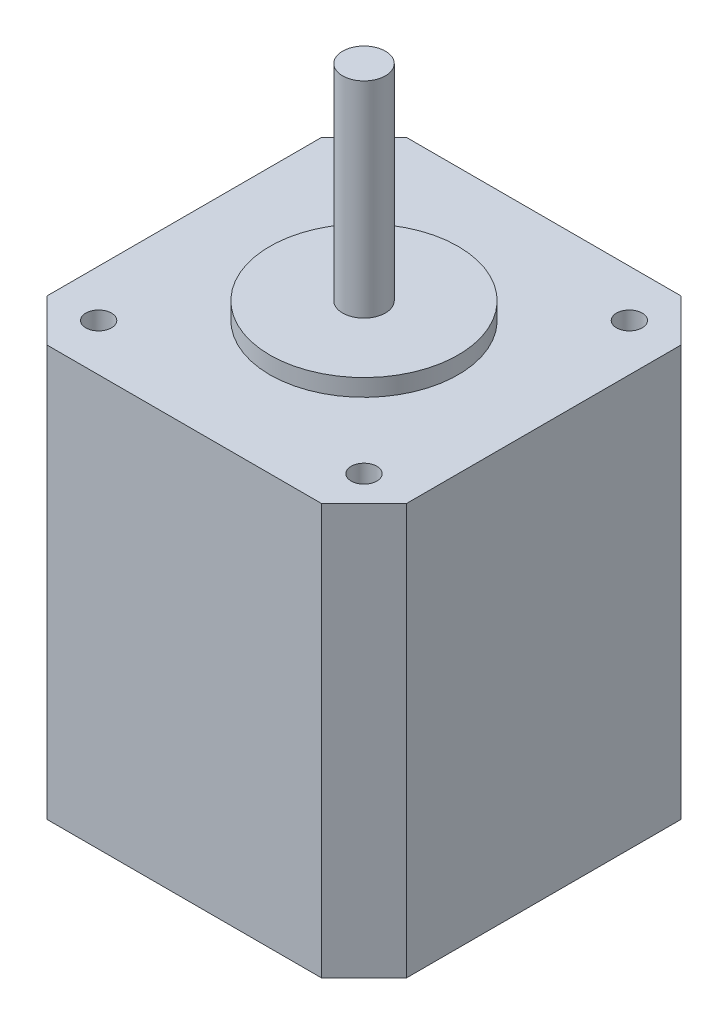
SolidWorks part; units mm, degrees
ref_plane "Front Plane" through (0, 0, 0) normal (0, 0, 1) x (1, 0, 0)
ref_plane "Top Plane" through (0, 0, 0) normal (0, 1, 0) x (1, 0, 0)
ref_plane "Right Plane" through (0, 0, 0) normal (1, 0, 0) x (0, 0, -1)
sketch "Sketch1" plane through (0, 0, 0) normal (0, 1, 0) x (1, 0, 0)
  line L1 (0, 0) -> (42, 0)
  line L2 (0, 0) -> (0, 42)
  line L3 (0, 42) -> (42, 42)
  line L4 (42, 0) -> (42, 42)
  line L5 (0, 0) -> (42, 42) construction
  line L6 (0, 42) -> (42, 0) construction
  point P4 (21, 21)
  dimension "D1" = 42
  dimension "D2" = 42
extrude "Boss-Extrude1" add sketch "Sketch1" along normal blind 48
sketch "Sketch5" plane through (0, 48, 0) normal (0, 1, 0) x (1, 0, 0)
  line L0 (42, 21) -> (0, 21) construction
  line L1 (42, 0) -> (42, 42) construction
  line L2 (0, 42) -> (0, 0) construction
  line L3 (21, 0) -> (21, 42) construction
  line L4 (0, 0) -> (42, 0) construction
  line L5 (42, 42) -> (0, 42) construction
  circle A0 centre (21, 21) radius 11
  dimension "D1" = 22
extrude "Boss-Extrude4" add sketch "Sketch5" along normal blind 2
sketch "Sketch6" plane through (0, 50, 0) normal (0, 1, 0) x (1, 0, 0)
  circle A0 centre (21, 21) radius 2.5
  dimension "D1" = 5
extrude "Boss-Extrude5" add sketch "Sketch6" along normal blind 24
sketch "Sketch8" plane through (0, 48, 0) normal (0, 1, 0) x (1, 0, 0)
  line L0 (36.5, 42) -> (36.5, 0) construction
  line L1 (42, 42) -> (0, 42) construction
  line L2 (0, 0) -> (42, 0) construction
  line L3 (42, 5.5) -> (0, 5.5) construction
  line L4 (42, 0) -> (42, 42) construction
  line L5 (0, 42) -> (0, 0) construction
  line L6 (42, 21) -> (0, 21) construction
  line L7 (21, 42) -> (21, 0) construction
  circle A0 centre (36.5, 5.5) radius 1.5
  circle A1 centre (36.5, 36.5) radius 1.5
  circle A2 centre (5.5, 5.5) radius 1.5
  circle A3 centre (5.5, 36.5) radius 1.5
  dimension "D3" = 3
  dimension "D1" = 15.5
  dimension "D2" = 15.5
extrude "Cut-Extrude1" cut sketch "Sketch8" against normal blind 4.5
sketch "Sketch9" plane through (0, 48, 0) normal (0, 1, 0) x (1, 0, 0)
  line L0 (0, 4.9497) -> (4.9497, 0)
  line L1 (0, 42) -> (0, 0) construction
  line L2 (0, 0) -> (42, 0) construction
  line L3 (37.0503, 0) -> (42, 4.9497)
  line L4 (42, 0) -> (42, 42) construction
  line L5 (37.0503, 42) -> (42, 37.0503)
  line L6 (42, 42) -> (0, 42) construction
  line L7 (0, 37.0503) -> (4.9497, 42)
  line L8 (4.9497, 42) -> (0, 42)
  line L9 (0, 42) -> (0, 37.0503)
  line L10 (0, 4.9497) -> (0, 0)
  line L11 (0, 0) -> (4.9497, 0)
  line L12 (42, 4.9497) -> (42, 0)
  line L13 (42, 0) -> (37.0503, 0)
  line L14 (42, 37.0503) -> (42, 42)
  line L15 (42, 42) -> (37.0503, 42)
  point P17 (28.0386, 42)
  point P18 (42, 35.8289)
  point P26 (35.1713, 42)
  point P27 (0, 36.7336)
  dimension "D1" = 7
  dimension "D2" = 7
  dimension "D3" = 7
  dimension "D4" = 7
extrude "Cut-Extrude2" cut sketch "Sketch9" against normal through all
